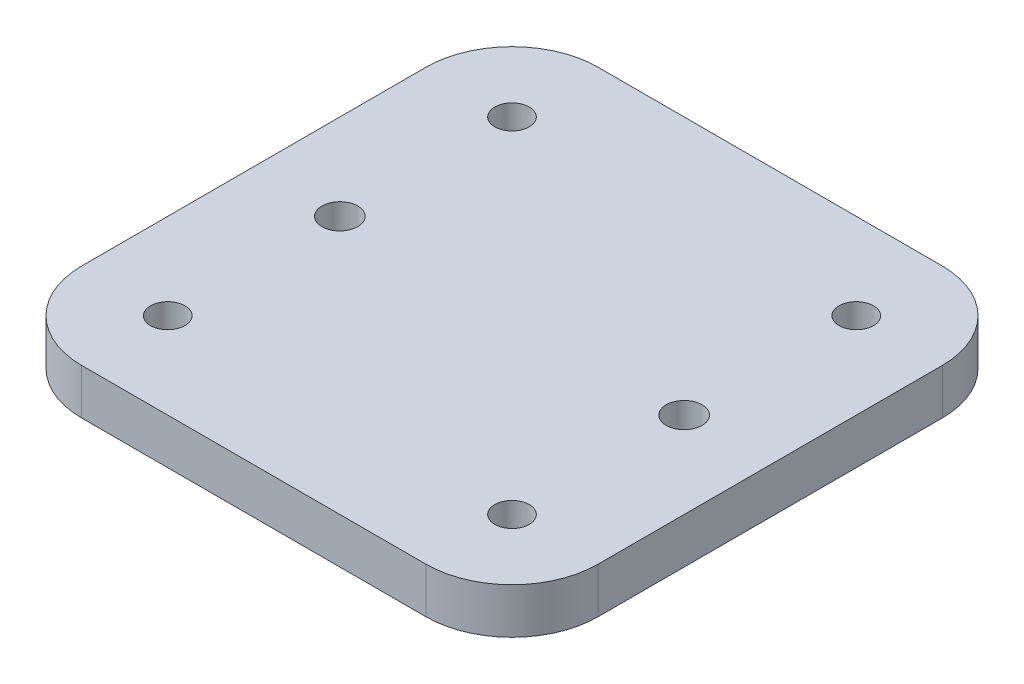
SolidWorks part; units mm, degrees
ref_plane "Front Plane" through (0, 0, 0) normal (0, 0, 1) x (1, 0, 0)
ref_plane "Top Plane" through (0, 0, 0) normal (0, 1, 0) x (1, 0, 0)
ref_plane "Right Plane" through (0, 0, 0) normal (1, 0, 0) x (0, 0, -1)
sketch "Sketch1" plane through (0, 0, 0) normal (0, 1, 0) x (1, 0, 0)
  line L1 (-24, -36) -> (24, -36)
  line L2 (-36, -24) -> (-36, 24)
  line L3 (-24, 36) -> (24, 36)
  line L4 (36, -24) -> (36, 24)
  line L5 (-36, -36) -> (36, 36) construction
  line L6 (-36, 36) -> (36, -36) construction
  arc A0 (24, 36) -> (36, 24) centre (24, 24) cw
  arc A1 (24, -36) -> (36, -24) centre (24, -24) ccw
  arc A2 (-24, -36) -> (-36, -24) centre (-24, -24) cw
  arc A3 (-36, 24) -> (-24, 36) centre (-24, 24) cw
  point P0 (0, 0)
  dimension "D1" = 12
  dimension "D2" = 72
  dimension "D3" = 72
extrude "Boss-Extrude1" add sketch "Sketch1" along normal blind 6.35
sketch "Sketch2" plane through (0, 6.35, 0) normal (0, 1, 0) x (1, 0, 0)
  line L0 (-36, 0) -> (36, 0) construction
  line L1 (-36, 24) -> (-36, -24) construction
  line L2 (36, -24) -> (36, 24) construction
  line L3 (-36, 12) -> (36, 12) construction
  circle A0 centre (-24, 24) radius 12 construction
  circle A1 centre (-24, 24) radius 2.4
  arc A2 (-24, 36) -> (-36, 24) centre (-24, 24) ccw construction
  circle A3 centre (24, 24) radius 2.4
  circle A4 centre (24, -24) radius 2.4
  circle A5 centre (-24, -24) radius 2.4
  dimension "D3" = 4.8
  dimension "D1" = 24
  dimension "D2" = 2
  dimension "D4" = 2
extrude "Cut-Extrude1" cut sketch "Sketch2" against normal through all
sketch "Sketch3" plane through (0, 6.35, 0) normal (0, 1, 0) x (1, 0, 0)
  line L0 (-24, 0) -> (24, 0) construction
  line L1 (-24, 24) -> (-24, -24) construction
  line L2 (24, 24) -> (24, -24) construction
  circle A1 centre (-24, 0) radius 2.5
  circle A3 centre (24, 0) radius 2.5
  dimension "D1" = 5
extrude "Cut-Extrude2" cut sketch "Sketch3" against normal through all
